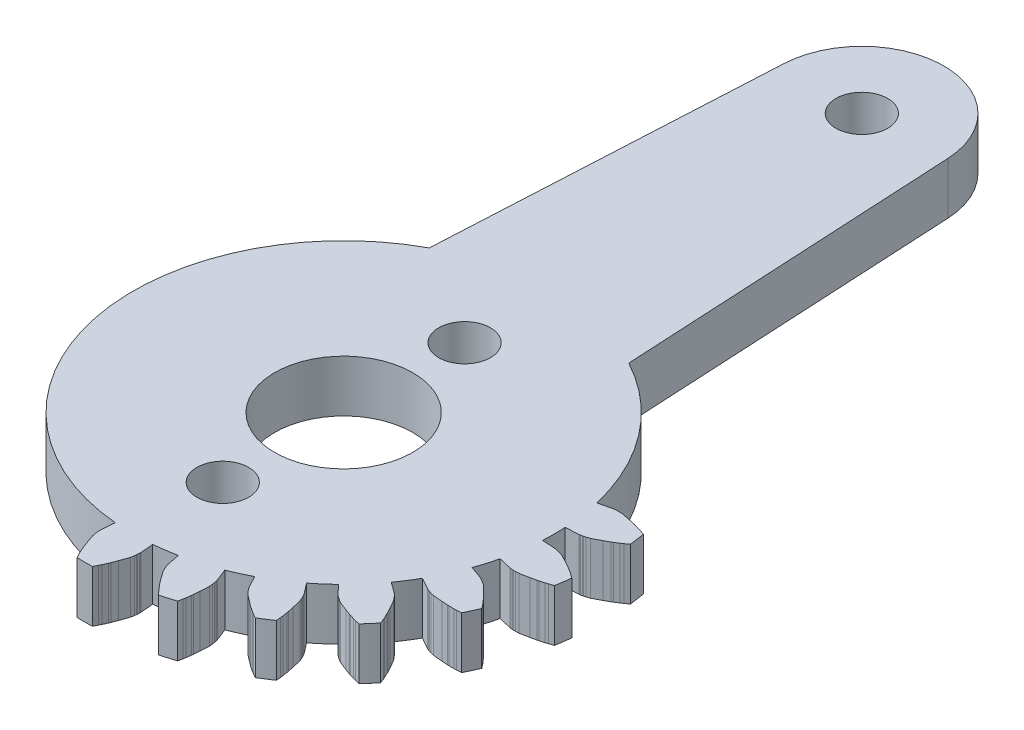
SolidWorks part; units mm, degrees
material "普通碳钢"
ref_plane "前视" through (0, 0, 0) normal (0, 0, 1) x (1, 0, 0)
ref_plane "上视" through (0, 0, 0) normal (0, 1, 0) x (1, 0, 0)
ref_plane "右视" through (0, 0, 0) normal (1, 0, 0) x (0, 0, -1)
sketch "草图1" plane through (0, 0, 0) normal (0, 1, 0) x (1, 0, 0)
  line L0 (39.751, 40.5224) -> (39.6866, 41.2679)
  line L1 (39.6866, 41.2679) -> (39.6851, 41.3287)
  line L2 (39.6851, 41.3287) -> (39.6859, 41.3577)
  line L3 (39.6859, 41.3577) -> (39.6916, 41.4528)
  line L4 (39.6916, 41.4528) -> (39.6929, 41.4698)
  line L5 (39.6929, 41.4698) -> (39.6966, 41.5042)
  line L6 (39.6966, 41.5042) -> (39.712, 41.6258)
  line L7 (39.712, 41.6258) -> (39.7121, 41.6267)
  line L8 (39.7121, 41.6267) -> (39.7482, 41.8247)
  line L9 (39.9295, 42.3366) -> (40.044, 42.6442)
  line L10 (40.044, 42.6442) -> (40.0454, 42.6478)
  line L11 (40.0454, 42.6478) -> (40.0855, 42.7398)
  line L12 (40.0855, 42.7398) -> (40.1995, 42.9971)
  line L13 (41.9203, 40.5224) -> (41.9848, 41.2679)
  line L14 (41.9848, 41.2679) -> (41.9862, 41.3287)
  line L15 (41.9862, 41.3287) -> (41.9855, 41.3577)
  line L16 (41.9855, 41.3577) -> (41.9797, 41.4528)
  line L17 (41.9797, 41.4528) -> (41.9784, 41.4698)
  line L18 (41.9784, 41.4698) -> (41.9748, 41.5042)
  line L19 (41.9748, 41.5042) -> (41.9594, 41.6258)
  line L20 (41.9594, 41.6258) -> (41.9592, 41.6267)
  line L21 (41.9592, 41.6267) -> (41.9231, 41.8247)
  line L22 (41.7419, 42.3366) -> (41.6274, 42.6442)
  line L23 (41.6274, 42.6442) -> (41.626, 42.6478)
  line L24 (41.626, 42.6478) -> (41.5858, 42.7398)
  line L25 (41.5858, 42.7398) -> (41.4718, 42.9971)
  circle A0 centre (40.8357, 28.3833) radius 12.1875 construction
  arc A1 (39.751, 40.5224) -> (41.9203, 40.5224) centre (40.8357, 28.3833) cw
  arc A2 (41.9231, 41.8247) -> (41.7419, 42.3366) centre (25.8953, 36.4382) ccw
  arc A4 (39.9295, 42.3366) -> (39.7482, 41.8247) centre (55.7761, 36.4382) ccw
  arc A5 (40.2653, 43.1347) -> (40.1995, 42.9971) centre (42.6892, 41.8899) ccw
  arc A6 (40.3945, 43.3768) -> (40.2653, 43.1347) centre (48.1168, 39.1026) ccw
  arc A11 (41.4718, 42.9971) -> (41.406, 43.1347) centre (38.9822, 41.8899) ccw
  arc A12 (41.406, 43.1347) -> (41.2769, 43.3768) centre (33.5546, 39.1026) ccw
  arc A13 (41.2769, 43.3768) -> (40.3945, 43.3768) centre (40.8357, 28.3833) ccw
  dimension "D1" = 24.375
extrude "凸台-拉伸1" add sketch "草图1" along normal blind 3 contours A4 L8 L7 L6 L5 L4 L3 L2 L1 L0 A1 L13 L14 L15 L16 L17 L18 L19 L20 L21 A2 L22 L23 L24 L25 A11 A12 A13 A6 A5 L12 L11 L10 L9
sketch "草图2" plane through (0, 0, 0) normal (0, -1, 0) x (1, 0, 0)
  circle A0 centre (40.8357, -28.3833) radius 12.1875
  circle A1 centre (40.8357, -28.3833) radius 4
  circle A2 centre (40.8357, -28.3833) radius 7 construction
  circle A3 centre (40.8357, -21.3833) radius 1.5
  circle A4 centre (40.8357, -35.3833) radius 1.5
  dimension "D1" = 8
  dimension "D2" = 24.375
  dimension "D3" = 14
  dimension "D4" = 3
  dimension "D5" = 3
extrude "凸台-拉伸2" add sketch "草图2" against normal blind 3
pattern_circular "阵列(圆周)2" count 22 over 360 about axis through (40.8357, 3, -28.3833) along (0, -1, 0) of "凸台-拉伸1"
sketch "草图3" plane through (0, 0, 0) normal (0, -1, 0) x (-1, 0, 0)
  circle A0 centre (-40.8357, 28.3833) radius 13.75
  dimension "D1" = 27.5
sketch "草图5" plane through (0, 0, 0) normal (0, -1, 0) x (1, 0, 0)
  line L0 (40.8357, -19.8833) -> (40.8357, -63.1398) construction
  line L1 (45.5857, -58.6327) -> (46.6107, -39.1157)
  line L2 (36.0857, -58.6327) -> (35.0607, -39.1157)
  circle A0 centre (40.8357, -21.3833) radius 1.5 construction
  circle A2 centre (40.8357, -28.3833) radius 12.1875 construction
  arc A3 (53.0056, -29.0373) -> (53.0056, -27.7293) centre (40.8357, -28.3833) ccw construction
  arc A4 (36.0857, -58.6327) -> (45.5857, -58.6327) centre (40.8357, -58.3833) ccw
  circle A5 centre (40.8357, -58.3833) radius 1.5
  arc A6 (35.0607, -39.1157) -> (46.6107, -39.1157) centre (40.8357, -28.3833) ccw
  dimension "D4" = 3
  dimension "D1" = 11.55
  dimension "D2" = 9.5
  dimension "D3" = 30
extrude "凸台-拉伸3" add sketch "草图5" against normal blind 3
sketch "草图7" plane through (0, 0, 0) normal (0, -1, 0) x (1, 0, 0)
  line L0 (36.0857, -58.6327) -> (34.9723, -37.4337) construction
  line L1 (35.0751, -39.3907) -> (36.0857, -58.6327) construction
  line L2 (45.5857, -58.6327) -> (46.7591, -36.2892) construction
  line L3 (45.5857, -58.6327) -> (46.5962, -39.3907) construction
  line L4 (35.0607, -39.1157) -> (35.0751, -39.3907)
  line L5 (35.0751, -39.3907) -> (34.8365, -39.8437)
  line L6 (34.8365, -39.8437) -> (33.6211, -45.0698)
  line L7 (33.6211, -45.0698) -> (23.2947, -35.4215)
  line L8 (23.2947, -35.4215) -> (25.1891, -22.1682)
  line L9 (25.1891, -22.1682) -> (31.4308, -11.204)
  line L10 (31.4308, -11.204) -> (37.9696, -9.817)
  line L11 (37.9696, -9.817) -> (39.751, -16.2441)
  line L12 (46.6107, -39.1157) -> (46.5962, -39.3907)
  line L13 (46.5962, -39.3907) -> (47.0142, -42.3632)
  line L14 (52.3284, -32.4394) -> (55.4375, -32.4394)
  line L15 (55.4375, -32.4394) -> (53.5277, -41.7128)
  line L16 (53.5277, -41.7128) -> (47.0142, -42.3632)
  arc A0 (35.0607, -39.1157) -> (39.751, -16.2441) centre (40.8357, -28.3833) cw
  circle A1 centre (40.8357, -28.3833) radius 4 construction
  circle A2 centre (40.8357, -28.3833) radius 12.1875 construction
  arc A3 (46.6107, -39.1157) -> (52.3284, -32.4394) centre (40.8357, -28.3833) ccw
extrude "切除-拉伸1" cut sketch "草图7" against normal blind 3
sketch "草图8" plane through (0, 0, 0) normal (0, -1, 0) x (1, 0, 0)
  line L0 (40.8357, -35.3833) -> (40.8357, -21.3833)
